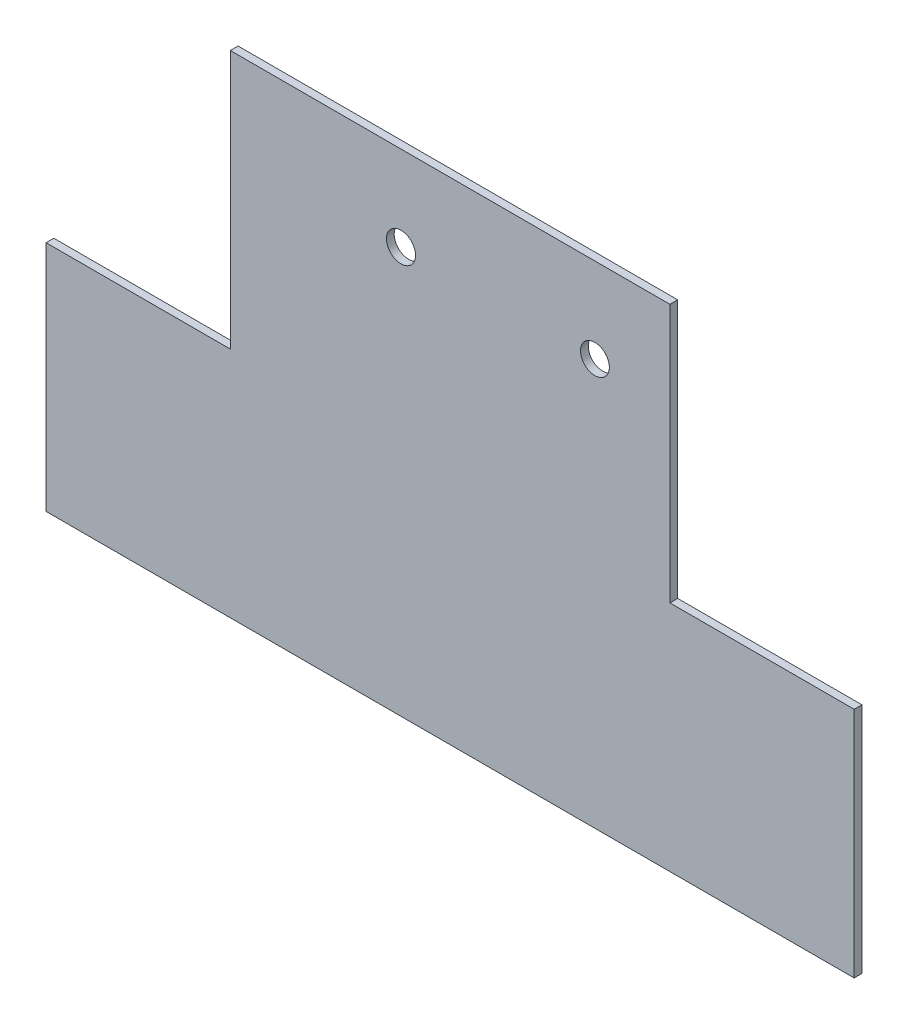
SolidWorks part; units mm, degrees
ref_plane "Спереди" through (0, 0, 0) normal (0, 0, 1) x (1, 0, 0)
ref_plane "Сверху" through (0, 0, 0) normal (0, 1, 0) x (1, 0, 0)
ref_plane "Справа" through (0, 0, 0) normal (1, 0, 0) x (0, 0, -1)
sketch "Эскиз1" plane through (0, 0, 0) normal (0, 0, 1) x (1, 0, 0)
  line L0 (28.5, 36) -> (28.5, 76)
  line L1 (0, 0) -> (125, 0)
  line L2 (0, 0) -> (0, 36)
  line L3 (0, 36) -> (28.5, 36)
  line L4 (125, 0) -> (125, 36)
  line L5 (28.5, 76) -> (96.5, 76)
  line L6 (96.5, 76) -> (96.5, 36)
  line L7 (96.5, 36) -> (125, 36)
  line L8 (84.9, 62.87) -> (54.9, 62.87) construction
  circle A0 centre (54.9, 62.87) radius 2.25
  circle A1 centre (84.9, 62.87) radius 2.2273
  dimension "D7" = 30
  dimension "D8" = 11.6
  dimension "D1" = 36
  dimension "D2" = 125
  dimension "D3" = 68
  dimension "D4" = 40
  dimension "D5" = 28.5
  dimension "D6" = 13.13
base flange "Базовая кромка1" sketch "Эскиз1" thickness 1.2 reverse thickness direction no parameters "D1"=0.7366
sketch "Сгиб-Линии1" plane through (0, 0, 0) normal (0, 1, 0) x (1, 0, 0)
sketch "Граничная рамка1" plane through (0, 0, 0) normal (0, 1, 0) x (1, 0, 0)
sheet metal parameters "Листовой металл3" thickness 1.2 parameters "D1"=0.7366
flat pattern "Развертка3" [suppressed]
sketch "Сгиб-Линии2" plane through (0, 0, 0) normal (0, 1, 0) x (1, 0, 0)
sketch "Граничная рамка2" [suppressed] plane through (0, 0, 0) normal (0, 1, 0) x (1, 0, 0)
